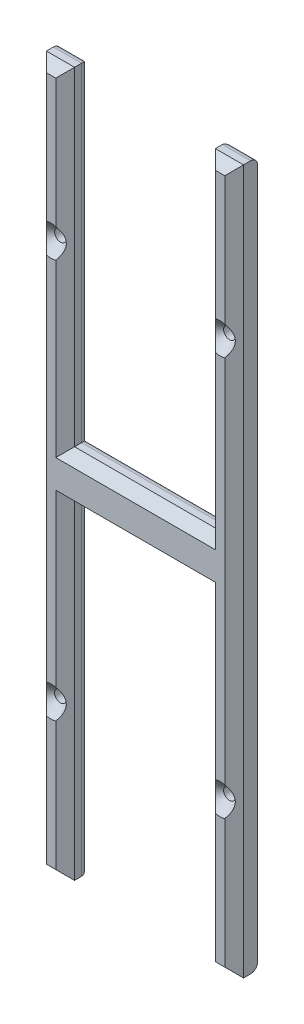
SolidWorks part; units mm, degrees
ref_plane "Front Plane" through (0, 0, 0) normal (0, 0, 1) x (1, 0, 0)
ref_plane "Top Plane" through (0, 0, 0) normal (0, 1, 0) x (1, 0, 0)
ref_plane "Right Plane" through (0, 0, 0) normal (1, 0, 0) x (0, 0, -1)
sketch "Sketch1" plane through (0, 0, 0) normal (0, 0, 1) x (1, 0, 0)
  line L0 (-210, 750) -> (-150, 750)
  line L1 (-150, 750) -> (-150, 50)
  line L2 (-150, 50) -> (150, 50)
  line L3 (150, 50) -> (150, 750)
  line L4 (150, 750) -> (210, 750)
  line L5 (210, 750) -> (210, -750)
  line L6 (210, -750) -> (150, -750)
  line L7 (150, -750) -> (150, -50)
  line L8 (150, -50) -> (-150, -50)
  line L9 (-150, -50) -> (-150, -750)
  line L10 (-150, -750) -> (-210, -750)
  line L11 (-210, -750) -> (-210, 750)
  line L12 (0, -55) -> (0, 55) construction
  line L13 (55, 0) -> (-55, 0) construction
  circle A0 centre (180, 425) radius 12.5
  circle A1 centre (-180, 425) radius 12.5
  circle A2 centre (180, -425) radius 12.5
  circle A3 centre (-180, -425) radius 12.5
  point P2 (0, 50)
  dimension "D6" = 25
  dimension "D1" = 700
  dimension "D2" = 300
  dimension "D3" = 60
  dimension "D4" = 1500
  dimension "D5" = 325
  dimension "D7" = 325
extrude "Boss-Extrude1" add sketch "Sketch1" along normal blind 50
chamfer "Chamfer1" distance 20 angle 45 16 edges at (-180, 750, 50) (-150, 400, 50) (0, 50, 50) (150, 400, 50) (180, 750, 50) (210, 0, 50) (180, -750, 50) (150, -400, 50) (0, -50, 50) (-150, -400, 50) (-180, -750, 50) (-210, 0, 50) (192.5, 425, 50) (-167.5, -425, 50) (167.5, -425, 50) (-192.5, 425, 50)
fillet "Fillet1" radius 15 10 edges at (-180, -750, 0) (180, -750, 0) (-180, 750, 0) (180, 750, 0) (-150, -400, 0) (150, -400, 0) (0, -50, 0) (-150, 400, 0) (0, 50, 0) (150, 400, 0)
fillet "Fillet2" radius 3 4 edges at (192.5, 425, 0) (-167.5, -425, 0) (167.5, -425, 0) (-192.5, 425, 0)
